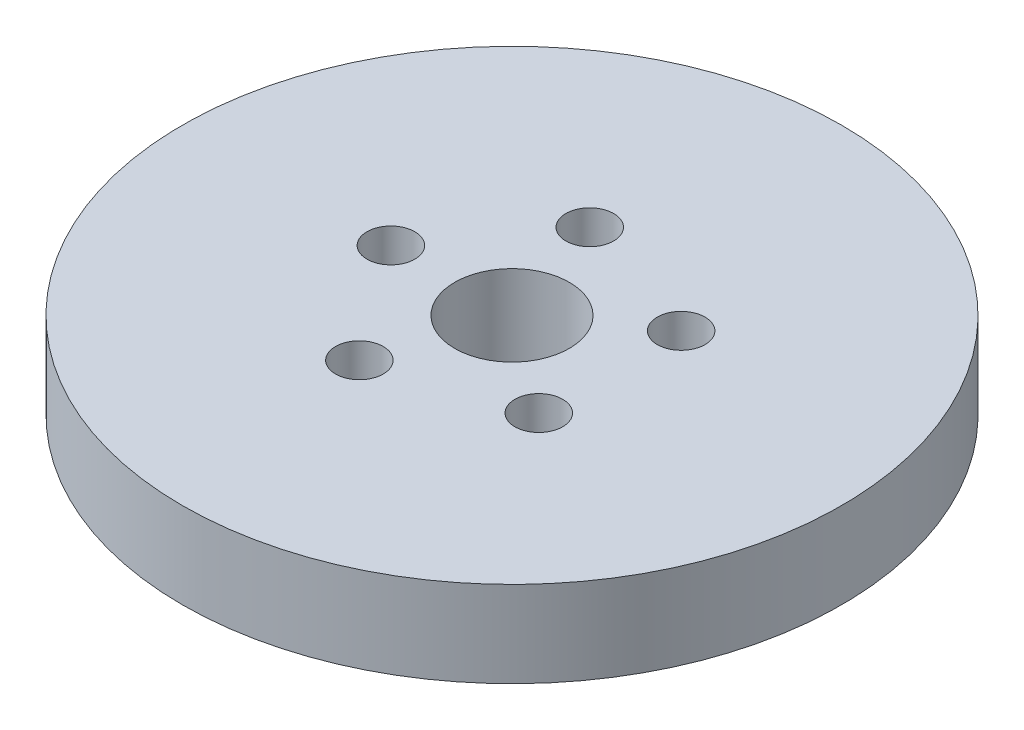
SolidWorks part; units mm, degrees
ref_plane "Front Plane" through (0, 0, 0) normal (0, 0, 1) x (1, 0, 0)
ref_plane "Top Plane" through (0, 0, 0) normal (0, 1, 0) x (1, 0, 0)
ref_plane "Right Plane" through (0, 0, 0) normal (1, 0, 0) x (0, 0, -1)
sketch "Sketch1" plane through (0, 0, 0) normal (0, 1, 0) x (1, 0, 0)
  circle A0 centre (0, 0) radius 57.5
  dimension "FLANGE_OD" = 115
extrude "Boss-Extrude1" add sketch "Sketch1" along normal blind 15
sketch "Sketch2" plane through (0, 0, 0) normal (0, 1, 0) x (1, 0, 0)
  circle A0 centre (0, 0) radius 10
  dimension "BORE_D" = 20
extrude "Cut-Extrude1" cut sketch "Sketch2" along normal through all
sketch "Sketch3" plane through (0, 15, 0) normal (0, 1, 0) x (1, 0, 0)
  circle A0 centre (0, 0) radius 21.131 construction
  circle A1 centre (-21.131, 0) radius 4.1647
  dimension "BOLT_D" = 8.3294
  dimension "BOLT_PCD" = 42.262
extrude "Cut-Extrude2" cut sketch "Sketch3" against normal blind 9.5022
pattern_circular "CirPattern1" count 5 over 360 about axis through (0, 0, 0) along (0, 1, 0) of "Cut-Extrude2"
